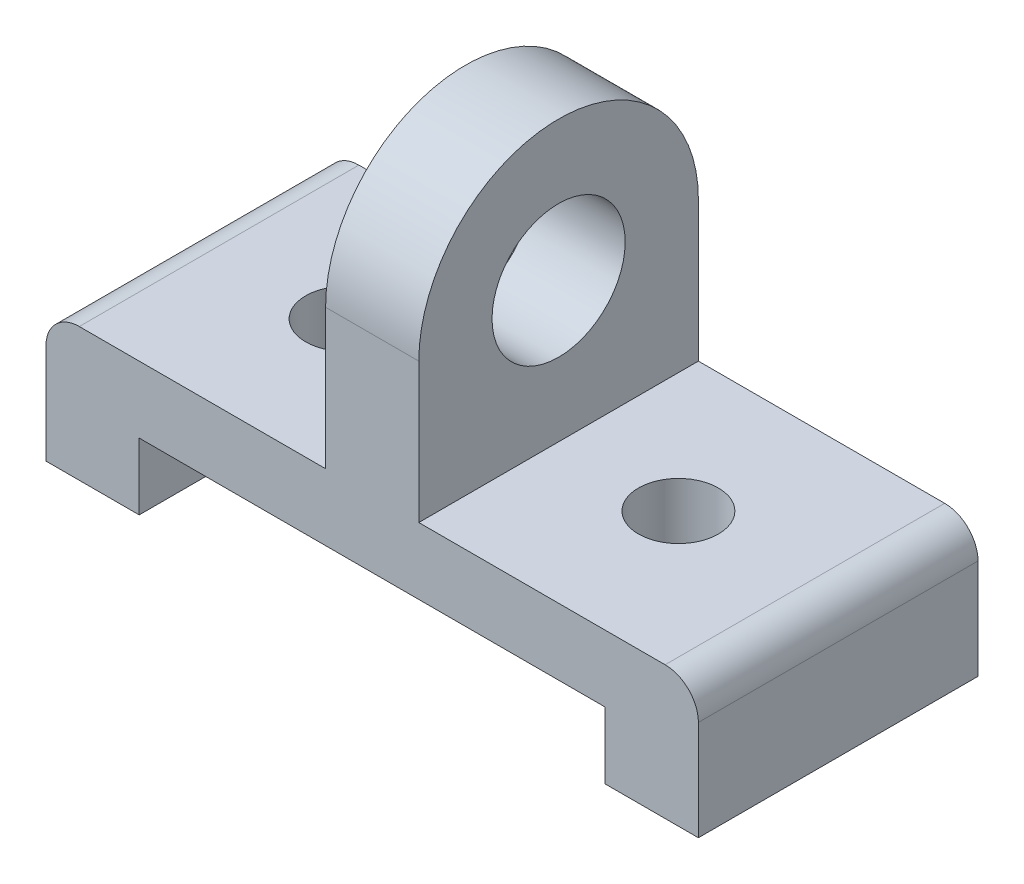
SolidWorks part; units mm, degrees
ref_plane "Front Plane" through (0, 0, 0) normal (0, 0, 1) x (1, 0, 0)
ref_plane "Top Plane" through (0, 0, 0) normal (0, 1, 0) x (1, 0, 0)
ref_plane "Right Plane" through (0, 0, 0) normal (1, 0, 0) x (0, 0, -1)
sketch "Sketch1" plane through (0, 0, 0) normal (0, 1, 0) x (1, 0, 0)
  line L0 (0, 21) -> (0, -21) construction
  line L1 (49, 21) -> (-49, 21)
  line L2 (49, 21) -> (49, -21)
  line L3 (49, -21) -> (-49, -21)
  line L4 (-49, 21) -> (-49, -21)
  line L5 (49, 21) -> (-49, -21) construction
  line L6 (49, -21) -> (-49, 21) construction
  line L7 (-49, 21) -> (-49, -21)
  circle A0 centre (25, 0) radius 6
  circle A1 centre (-25, 0) radius 6
  point P0 (0, 0)
  point P12 (0, 0)
  dimension "D3" = 12
  dimension "D1" = 42
  dimension "D2" = 98
  dimension "D4" = 21
  dimension "D5" = 24
extrude "Boss-Extrude1" add sketch "Sketch1" along normal blind 10 and the other way blind 0.01 contours L1 L4 L3 L2 A0 A1 region at (0, 0, 0)
fillet "Fillet1" radius 5 1 edges at (-49, 10, 0)
fillet "Fillet2" radius 5 1 edges at (49, 10, 0)
sketch "Sketch3" plane through (0, -0.01, 0) normal (0, -1, 0) x (1, 0, 0)
  line L0 (0, -21) -> (0, 21) construction
  line L1 (49, -21) -> (-49, -21) construction
  line L2 (49, 21) -> (-49, 21) construction
  line L3 (49, -21) -> (35, -21)
  line L4 (-49, 21) -> (-35, 21)
  line L5 (-49, 21) -> (-49, -21)
  line L6 (-49, -21) -> (-35, -21)
  line L7 (-35, 21) -> (-35, -21)
  line L8 (35, 21) -> (35, -21)
  line L9 (49, 21) -> (35, 21)
  line L10 (49, 21) -> (49, -21)
  point P11 (0, 0)
  dimension "D1" = 14
extrude "Boss-Extrude4" add sketch "Sketch3" along normal blind 10 contours L7 L6 L5 L4
sketch "Sketch10" plane through (0, -0.01, 0) normal (0, -1, 0) x (1, 0, 0)
  line L0 (49, -21) -> (-35, -21) construction
  line L1 (49, 21) -> (35, 21)
  line L2 (49, 21) -> (49, -21)
  line L3 (49, -21) -> (35, -21)
  line L4 (35, 21) -> (35, -21)
  dimension "D1" = 14
extrude "Boss-Extrude5" add sketch "Sketch10" along normal blind 10
sketch "Sketch11" plane through (0, 10, 0) normal (0, 1, 0) x (1, 0, 0)
  line L0 (0, 21) -> (0, -21) construction
  line L1 (44, 21) -> (-44, 21) construction
  line L2 (44, -21) -> (-44, -21) construction
  line L4 (7, -21) -> (-7, -21)
  line L5 (7, -21) -> (7, 21)
  line L6 (7, 21) -> (-7, 21)
  line L7 (-7, -21) -> (-7, 21)
  line L8 (7, -21) -> (-7, 21) construction
  line L9 (7, 21) -> (-7, -21) construction
  point P6 (0, 0)
  point P12 (0, 0)
  dimension "D1" = 14
  dimension "D2" = 42
extrude "Boss-Extrude6" add sketch "Sketch11" along normal blind 42
fillet "Fillet3" 2 edges at (0, 52, 21) (0, 52, -21) type full round first side face at (0, 8.2865, 21) second side face at (0, 8.2865, -21) middle face at (0, 52, 0)
sketch "Sketch12" plane through (7, 0, 0) normal (1, 0, 0) x (0, 0, -1)
  line L0 (-21, 10) -> (21, 10) construction
  circle A0 centre (0, 31) radius 10
  dimension "D1" = 20
  dimension "D2" = 21
extrude "Cut-Extrude1" cut sketch "Sketch12" against normal through all both and the other way through all
